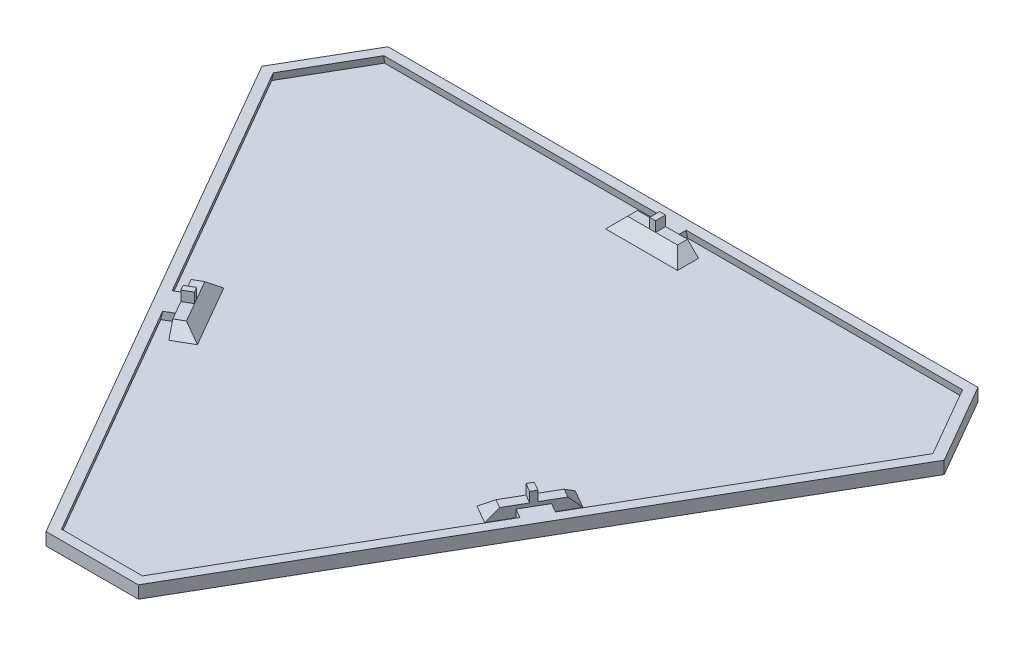
SolidWorks part; units mm, degrees
ref_plane "Plan de face" through (0, 0, 0) normal (0, 0, 1) x (1, 0, 0)
ref_plane "Plan de dessus" through (0, 0, 0) normal (0, 1, 0) x (1, 0, 0)
ref_plane "Plan de droite" through (0, 0, 0) normal (1, 0, 0) x (0, 0, -1)
sketch "Esquisse2" plane through (0, 0, 0) normal (0, 1, 0) x (1, 0, 0)
  line L3 (-59.0248, 44.7446) -> (-68.2624, 28.7446) construction
  line L4 (-59.0248, 44.7446) -> (59.0248, 44.7446) construction
  line L5 (68.2624, 28.7446) -> (9.2376, -73.4893) construction
  line L6 (-68.2624, 28.7446) -> (-59.0248, 44.7446)
  line L7 (59.0248, 44.7446) -> (68.2624, 28.7446)
  line L8 (9.2376, -73.4893) -> (-9.2376, -73.4893)
  line L9 (-68.2624, 28.7446) -> (-9.2376, -73.4893)
  line L10 (9.2376, -73.4893) -> (68.2624, 28.7446)
  line L11 (59.0248, 44.7446) -> (-59.0248, 44.7446)
  line L12 (-9.2376, -73.4893) -> (-68.2624, 28.7446) construction
  line L13 (-9.2376, -73.4893) -> (9.2376, -73.4893) construction
  line L14 (68.2624, 28.7446) -> (59.0248, 44.7446) construction
  point P16 (0, 0)
extrude "Boss.-Extru.2" add sketch "Esquisse2" along normal blind 1
sketch "Esquisse5" plane through (0, 1, 0) normal (0, 1, 0) x (1, 0, 0)
  line L19 (-68.2624, 28.7446) -> (-9.2376, -73.4893)
  line L20 (-9.2376, -73.4893) -> (9.2376, -73.4893)
  line L21 (9.2376, -73.4893) -> (68.2624, 28.7446)
  line L26 (68.2624, 28.7446) -> (59.0248, 44.7446)
  line L27 (59.0248, 44.7446) -> (-59.0248, 44.7446)
  line L32 (-59.0248, 44.7446) -> (-68.2624, 28.7446)
  line L37 (-68.2624, 28.7446) -> (-9.2376, -73.4893)
  line L38 (-9.2376, -73.4893) -> (9.2376, -73.4893)
  line L39 (9.2376, -73.4893) -> (68.2624, 28.7446)
  line L44 (68.2624, 28.7446) -> (59.0248, 44.7446)
  line L45 (59.0248, 44.7446) -> (-59.0248, 44.7446)
  line L50 (-59.0248, 44.7446) -> (-68.2624, 28.7446)
  point P1 (-2.1696, 44.7446)
  point P2 (39.8656, -20.4401)
  point P6 (-40, -20.4411)
  point P8 (-67.9143, 28.1417)
  point P9 (-58.3798, 44.7446)
  point P10 (67.7027, 27.7753)
  dimension "D1" = 0
extrude "Extru.-Mince1" add sketch "Esquisse5" along normal blind 1.5 draft 10 thin draft outward yes thin type one direction reverse wall 1.7
sketch "Esquisse6" plane through (0, 0, 0) normal (0, -1, 0) x (1, 0, 0)
  line L6 (-59.0248, -44.7446) -> (59.0248, -44.7446)
  line L7 (59.0248, -44.7446) -> (68.2624, -28.7446)
  line L8 (68.2624, -28.7446) -> (9.2376, 73.4893)
  line L9 (9.2376, 73.4893) -> (-9.2376, 73.4893)
  line L10 (-9.2376, 73.4893) -> (-68.2624, -28.7446)
  line L11 (-68.2624, -28.7446) -> (-59.0248, -44.7446)
  line L12 (-59.0248, -44.7446) -> (59.0248, -44.7446)
  line L13 (59.0248, -44.7446) -> (68.2624, -28.7446)
  line L14 (68.2624, -28.7446) -> (9.2376, 73.4893)
  line L15 (9.2376, 73.4893) -> (-9.2376, 73.4893)
  line L16 (-9.2376, 73.4893) -> (-68.2624, -28.7446)
  line L17 (-68.2624, -28.7446) -> (-59.0248, -44.7446)
  dimension "D1" = 0
extrude "Enlèv. de mat.-Extru.-Mince1" cut sketch "Esquisse6" against normal through all thin thin type one direction wall 1.5
sketch "Esquisse7" plane through (0, 1, 0) normal (0, 1, 0) x (1, 0, 0)
  line L0 (2.6, 44.7446) -> (-2.6, 44.7446)
  line L1 (2.6, 44.7446) -> (2.6, 40.6446)
  line L2 (-2.6, 44.7446) -> (-2.6, 40.6446)
  line L3 (2.6, 40.6446) -> (-2.6, 40.6446)
  line L4 (-59.0248, 44.7446) -> (59.0248, 44.7446) construction
  line L5 (33.8993, -22.574) -> (36.4993, -18.0707)
  line L6 (37.45, -24.624) -> (33.8993, -22.574)
  line L7 (37.45, -24.624) -> (40.05, -20.1207)
  line L8 (40.05, -20.1207) -> (36.4993, -18.0707)
  line L9 (-36.4993, -18.0707) -> (-33.8993, -22.574)
  line L10 (-40.05, -20.1207) -> (-36.4993, -18.0707)
  line L11 (-40.05, -20.1207) -> (-37.45, -24.624)
  line L12 (-37.45, -24.624) -> (-33.8993, -22.574)
  point P6 (0, 44.7446)
  point P7 (0, 44.7446)
  point P8 (8.869, 1.5896)
  point P19 (0, 0)
  dimension "D1" = 4.1
  dimension "D2" = 5.2
  dimension "D3" = 3
extrude "Boss.-Extru.5" add sketch "Esquisse7" along normal up to surface (1.5 mm away) up to face at (0, 2.5, 0)
sketch "Esquisse8" plane through (0, 1, 0) normal (0, 1, 0) x (1, 0, 0)
  line L0 (-2.6, 40.6446) -> (2.6, 40.6446) construction
  line L1 (-5, 40.6446) -> (5, 40.6446)
  line L2 (-5, 40.6446) -> (-5, 38.6446)
  line L3 (-5, 38.6446) -> (5, 38.6446)
  line L4 (5, 40.6446) -> (5, 38.6446)
  line L5 (37.6993, -15.9922) -> (32.6993, -24.6524)
  line L6 (37.6993, -15.9922) -> (35.9672, -14.9922)
  line L7 (35.9672, -14.9922) -> (30.9672, -23.6524)
  line L8 (32.6993, -24.6524) -> (30.9672, -23.6524)
  line L9 (-32.6993, -24.6524) -> (-37.6993, -15.9922)
  line L10 (-32.6993, -24.6524) -> (-30.9672, -23.6524)
  line L11 (-30.9672, -23.6524) -> (-35.9672, -14.9922)
  line L12 (-37.6993, -15.9922) -> (-35.9672, -14.9922)
  point P7 (0, 40.6446)
  point P8 (0, 40.6446)
  point P9 (14.9274, -3.6274)
  point P18 (0, 0)
  dimension "D1" = 10
  dimension "D2" = 2
  dimension "D3" = 3
extrude "Boss.-Extru.6" add sketch "Esquisse8" along normal blind 2.2
chamfer "Chanfrein1" distance 2.2 angle 45 9 edges at (-31.8333, 1, 24.1524) (-36.8333, 1, 15.4922) (-33.4672, 1, 19.3223) (36.8333, 1, 15.4922) (33.4672, 1, 19.3223) (31.8333, 1, 24.1524) (5, 1, -39.6446) (-5, 1, -39.6446) (0, 1, -38.6446)
sketch "Esquisse9" plane through (0, 3.2, 0) normal (0, 1, 0) x (1, 0, 0)
  line L0 (5, 40.6446) -> (-5, 40.6446) construction
  line L1 (0.6, 40.6446) -> (-0.6, 40.6446)
  line L2 (0.6, 40.6446) -> (0.6, 38.6446)
  line L3 (0.6, 38.6446) -> (-0.6, 38.6446)
  line L4 (-0.6, 40.6446) -> (-0.6, 38.6446)
  line L5 (-5, 38.6446) -> (5, 38.6446) construction
  line L6 (34.8993, -20.8419) -> (35.4993, -19.8027)
  line L7 (34.8993, -20.8419) -> (33.1672, -19.8419)
  line L8 (33.1672, -19.8419) -> (33.7672, -18.8027)
  line L9 (35.4993, -19.8027) -> (33.7672, -18.8027)
  line L10 (-35.4993, -19.8027) -> (-34.8993, -20.8419)
  line L11 (-35.4993, -19.8027) -> (-33.7672, -18.8027)
  line L12 (-33.7672, -18.8027) -> (-33.1672, -19.8419)
  line L13 (-34.8993, -20.8419) -> (-33.1672, -19.8419)
  point P6 (0, 40.6446)
  point P7 (0, 40.6446)
  point P10 (10.6324, 4.5655)
  point P21 (0, 0)
  dimension "D1" = 1.2
  dimension "D2" = 3
extrude "Boss.-Extru.7" add sketch "Esquisse9" along normal blind 2
